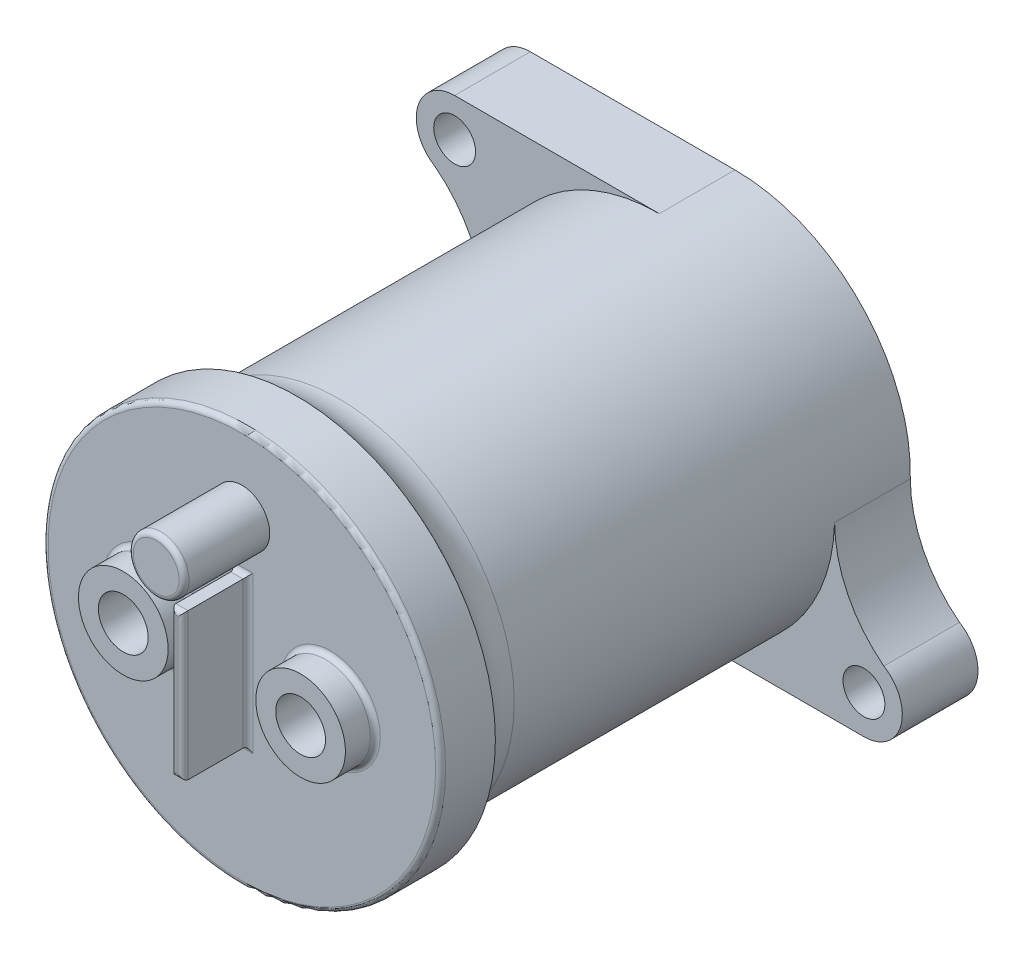
SolidWorks part; units mm, degrees
material "Custom Plastic"
ref_plane "X-Y Datum" through (0, 0, 0) normal (0, 0, 1) x (1, 0, 0)
ref_plane "X-Z Datum" through (0, 0, 0) normal (0, 1, 0) x (1, 0, 0)
ref_plane "Y-Z Datum" through (0, 0, 0) normal (1, 0, 0) x (0, 0, -1)
sketch "Sketch2" plane through (0, 0, 0) normal (0, 0, 1) x (1, 0, 0)
  circle A0 centre (0, 0) radius 17.6
  dimension "D1" = 35.2
extrude "Boss-Extrude1" add sketch "Sketch2" along normal blind 52.5
sketch "Sketch3" plane through (0, 0, 0) normal (0, 0, 1) x (1, 0, 0)
  line L0 (-17.6, 0) -> (17.6, 0) construction
  line L1 (-20.5412, 13.75) -> (20.5412, -13.75) construction
  line L2 (19.36, 0) -> (-19.36, 0) construction
  line L4 (0, 17.6) -> (0, -17.6) construction
  line L5 (-20.5412, 17.6) -> (0, 17.6)
  line L7 (-17.6, 0) -> (17.6, 0) construction
  line L8 (0, -17.6) -> (20.5412, -17.6)
  line L9 (0, -19.36) -> (0, 19.36) construction
  arc A6 (17.5941, -0.4546) -> (17.6, 0) centre (30.3137, -0.3916) cw
  arc A7 (17.5941, 0.4546) -> (17.6, 0) centre (30.3137, 0.3916) ccw
  circle A8 centre (0, 0) radius 17.6
  circle A9 centre (0, 0) radius 17.6
  arc A18 (-17.5941, -0.4546) -> (-17.6, 0) centre (-30.3137, -0.3916) ccw
  circle A19 centre (-20.5412, 13.75) radius 2.1
  circle A20 centre (-20.5412, 13.75) radius 3.85
  arc A21 (-22.5405, 10.4598) -> (-17.6, 0) centre (-30.3137, 0.3916) cw
  circle A22 centre (20.5412, -13.75) radius 2.1
  circle A23 centre (20.5412, -13.75) radius 3.85
  arc A24 (22.5405, -10.4598) -> (17.6, 0) centre (30.3137, -0.3916) cw
  point P4 (0, 0)
  point P10 (0, 0)
  point P23 (0, 0)
  dimension "D2" = 49.437
  dimension "D1" = 27.5
  dimension "D4" = 0
extrude "Boss-Extrude2" add sketch "Sketch3" along normal blind 7.6 contours A9 | A9 | A9 | A9 | A9 | A9 | A20 A19 | A23 A22 region at (-14.5084, 12.7029, 0) region at (-17.8959, 16.3954, 0) region at (14.5084, -12.7029, 0) region at (23.8019, -11.9159, 0)
sketch "Sketch4" plane through (0, 0, 52.5) normal (0, 0, 1) x (1, 0, 0)
  line L0 (-8.9, 0) -> (8.9, 0) construction
  line L1 (-0.615, 7.35) -> (0.615, 7.35)
  line L2 (-0.615, 7.35) -> (-0.615, -7.35)
  line L3 (-0.615, -7.35) -> (0.615, -7.35)
  line L4 (0.615, 7.35) -> (0.615, -7.35)
  line L5 (-0.615, 7.35) -> (0.615, -7.35) construction
  line L6 (-0.615, -7.35) -> (0.615, 7.35) construction
  circle A0 centre (-8.9, 0) radius 2.5
  circle A1 centre (8.9, 0) radius 2.5
  circle A2 centre (-8.9, 0) radius 4.5
  circle A3 centre (8.9, 0) radius 4.5
  point P0 (0, 0)
  point P11 (0, 0)
  dimension "D4" = 5
  dimension "D5" = 9
  dimension "D1" = 1.23
  dimension "D2" = 14.7
  dimension "D3" = 17.8
extrude "Boss-Extrude3" add sketch "Sketch4" along normal blind 3.5 contours L2 L1 L4 L3
sketch "Sketch5" plane through (0, 0, 52.5) normal (0, 0, 1) x (1, 0, 0)
  line L4 (0.615, 7.35) -> (-0.615, 7.35)
  line L5 (0.615, -7.35) -> (0.615, 7.35)
  line L6 (-0.615, -7.35) -> (0.615, -7.35)
  line L7 (-0.615, 7.35) -> (-0.615, -7.35)
  line L8 (0.615, 7.35) -> (-0.615, 7.35)
  line L9 (0.615, -7.35) -> (0.615, 7.35)
  line L10 (-0.615, -7.35) -> (0.615, -7.35)
  line L11 (-0.615, 7.35) -> (-0.615, -7.35)
  circle A1 centre (8.9, 0) radius 4.5
  circle A2 centre (8.9, 0) radius 4.5
  circle A3 centre (-8.9, 0) radius 4.5
  circle A4 centre (-8.9, 0) radius 4.5
  circle A5 centre (8.9, 0) radius 2.5
  circle A6 centre (8.9, 0) radius 2.5
  circle A7 centre (-8.9, 0) radius 2.5
  circle A8 centre (-8.9, 0) radius 2.5
  circle M22 centre (0, 0) radius 17.6
  line M23 (0.615, 7.35) -> (0.615, -7.35)
  line M24 (0.615, -7.35) -> (-0.615, -7.35)
  line M25 (-0.615, -7.35) -> (-0.615, 7.35)
  line M26 (-0.615, 7.35) -> (0.615, 7.35)
  dimension "D1" = 0
  dimension "D2" = 0
  dimension "D3" = 0
  dimension "D4" = 0
  dimension "D5" = 0
extrude "Cut-Extrude1" cut sketch "Sketch5" against normal blind 3 contours A4 A2 M22 M26 M23 M24 M25 | A8 | A6 region at (8.9, 0, 52.5) region at (-8.9, 0, 52.5) region at (-17.1022, 0, 52.5)
sketch "Sketch7" plane through (0, 0, 49.5) normal (0, 0, 1) x (1, 0, 0)
  circle A0 centre (0, 0) radius 19.95
  dimension "D1" = 39.9
extrude "Boss-Extrude5" add sketch "Sketch7" against normal blind 5.5
fillet "Fillet3" radius 5 1 edges at (17.6, 0, 44)
fillet "Fillet4" radius 0.5 11 edges at (-0.615, 0, 56) (0, 7.35, 56) (0.615, 0, 56) (0, -7.35, 56) (19.95, 0, 49.5) (-0.615, 0, 49.5) (0, -7.35, 49.5) (0.615, 0, 49.5) (0, 7.35, 49.5) (13.4, 0, 49.5) (-4.4, 0, 49.5)
sketch "Sketch8" plane through (0, 0, 52.5) normal (0, 0, 1) x (1, 0, 0)
  circle A0 centre (-8.9, 0) radius 2.5 construction
  circle A1 centre (8.9, 0) radius 2.5
  circle A2 centre (8.9, 0) radius 2.5
  circle A3 centre (-8.9, 0) radius 2.5
  dimension "D1" = 0
extrude "Cut-Extrude2" cut sketch "Sketch8" against normal blind 7
ref_plane "Plane1" through (0, 0, 0) normal (0.8035, 0.5952, 0) x (0, 0, 1)
sketch "Sketch10" plane through (0, 0, 49.5) normal (0, 0, 1) x (1, 0, 0)
  line L0 (0, 0) -> (0, 12.15) construction
  line L1 (0.615, 7.35) -> (-0.615, 7.35) construction
  circle A0 centre (0, 12.15) radius 2.8
  point P2 (0, 9.35)
  dimension "D1" = 5.6
  dimension "D2" = 2
extrude "Boss-Extrude6" add sketch "Sketch10" along normal blind 8.6
fillet "Fillet5" radius 0.5 1 edges at (2.8, 12.15, 58.1)
